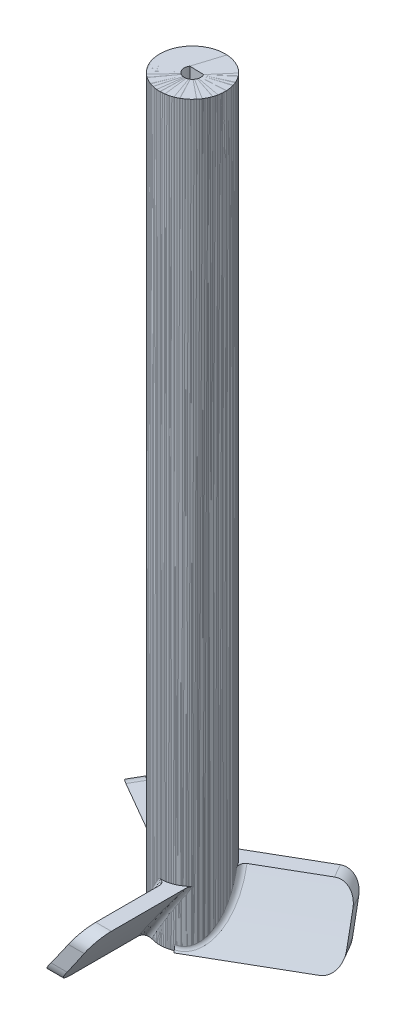
SolidWorks part; units mm, degrees
ref_plane "Front Plane" through (0, 0, 0) normal (0, 0, 1) x (1, 0, 0)
ref_plane "Top Plane" through (0, 0, 0) normal (0, 1, 0) x (1, 0, 0)
ref_plane "Right Plane" through (0, 0, 0) normal (1, 0, 0) x (0, 0, -1)
sketch "Sketch7" plane through (0, 0, 0) normal (0, 0, 1) x (1, 0, 0)
  line L0 (3.5176, 0) -> (-3.5176, 0) construction
  line L1 (6.849, 7) -> (4.9497, 7)
  line L2 (0, 0) -> (2, 0)
  arc A0 (0, 0) -> (4.9497, 7) centre (-91.3778, 69.8639) ccw
  arc A1 (6.849, 7) -> (2, 0) centre (-91.3778, 69.8639) cw
  dimension "D2" = 7
extrude "Boss-Extrude2" add sketch "Sketch7" along normal blind 15 contours A0 L1 A1 L2
fillet "Fillet1" radius 2 2 edges at (1, 0, 15) (5.8994, 7, 15)
sketch "Sketch10" plane through (0, 0, 0) normal (0, 1, 0) x (1, 0, 0)
  line L0 (0.3156, 0) -> (8.1957, 0) construction
  line L1 (4.9497, 0) -> (0, 0) construction
  line L2 (6.849, 0) -> (4.9497, 0) construction
  line L3 (2, 0) -> (6.849, 0) construction
  line L4 (4.2556, 0) -> (4.2556, -0.5251)
  line L5 (3.1481, -1000) -> (3.1481, 49000) construction
  circle A0 centre (4.2556, -0.5251) radius 3.9749
  point P5 (3.1481, 0)
  point P10 (-1.8519, 0)
  point P17 (3.1481, 0)
  dimension "D4" = 5
extrude "Boss-Extrude3" add sketch "Sketch10" along normal blind 90 contours A0 region at (0.3932, 0, 0.5251)
fillet "Fillet4" radius 0.7 2 edges at (1.2681, 1.6905, 3.147) (3.7358, 2.3821, 4.4659)
pattern_circular "CirPattern1" count 3 over 360 about axis through (4.2556, 90, 0.5251) along (0, -1, 0) of bodies 103 102
sketch "Sketch11" plane through (0, 90, 0) normal (0, 1, 0) x (1, 0, 0)
  line L0 (3.4046, 0) -> (5.1359, -0.0507)
  arc A1 (3.4046, 0) -> (5.1359, -0.0507) centre (4.2556, -0.5251) ccw
  circle A2 centre (4.2556, -0.5251) radius 3.9749 construction
extrude "Cut-Extrude1" cut sketch "Sketch11" against normal blind 40 contours A1 L0
equation "\"insidebladediameter\"=0.01"
equation "\"height\"= 0.007"
equation "\"bladethickness\"=0.002"
equation "\"insidebladeradius\"= \"insidebladediameter\" / 2"
equation "\"D1@Sketch7\"=\"bladethickness\""
equation "\"D2@Sketch7\"=\"height\""
equation "\"bladewidth\"= \"height\" * cos ( \"bladeangle\" )"
equation "\"bladelength\"= 0.015"
equation "\"D1@Boss-Extrude2\"=\"bladelength\""
equation "\"bladetipradius\"= 0.002"
equation "\"D1@Fillet1\"=\"bladetipradius\""
equation "\"fusedistance\"= 0.0045"
equation "\"motorrodheight\"=0.09"
equation "\"D1@Boss-Extrude3\"=\"motorrodheight\""
equation "\"numberofblades\"= 3"
equation "\"D1@CirPattern1\"=\"numberofblades\""
equation "\"roddiameter\"= ( \"bladewidth\" + 0.003 )"
equation "\"roddepth\"= 0.005"
equation "\"bladeangle\"= 45deg"
equation "\"m\"=1"
equation "\"flatfacedist\"= 0.0005"
equation "\"motorshaftdiameter\"=0.002"
equation "\"D1@Sketch11\"=\"motorshaftdiameter\"/2"
equation "\"D3@Sketch7\"=\"bladewidth\""
equation "\"D2@Sketch10\"=\"roddiameter\"/2-\"fusedistance\""
equation "\"D1@Sketch10\"=\"roddiameter\""
equation "\"D2@Sketch11\"=\"flatfacedist\""
equation "\"bladefilletradius\"= 0.0007"
equation "\"D1@Fillet4\"=\"bladefilletradius\""
